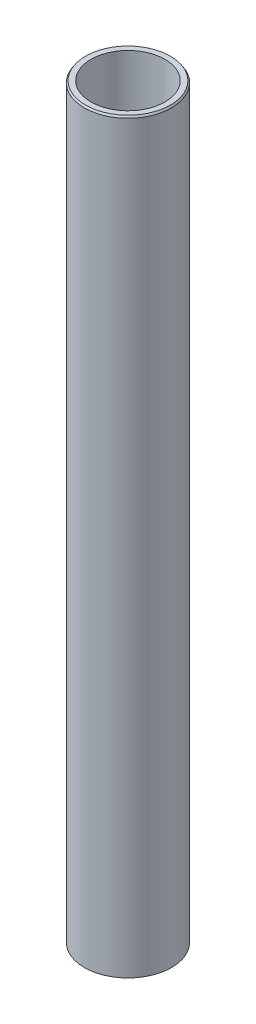
SolidWorks part; units mm, degrees
ref_plane "Front Plane" through (0, 0, 0) normal (0, 0, 1) x (1, 0, 0)
ref_plane "Top Plane" through (0, 0, 0) normal (0, 1, 0) x (1, 0, 0)
ref_plane "Right Plane" through (0, 0, 0) normal (1, 0, 0) x (0, 0, -1)
sketch "Sketch1" plane through (0, 0, 0) normal (0, 1, 0) x (1, 0, 0)
  circle A0 centre (0, 0) radius 35
  dimension "SHAFT_OD" = 70
extrude "Boss-Extrude1" add sketch "Sketch1" along normal blind 600
sketch "Sketch2" plane through (0, 0, 0) normal (0, 1, 0) x (1, 0, 0)
  circle A0 centre (0, 0) radius 29.685
  dimension "BORE_D" = 59.37
extrude "Cut-Extrude1" cut sketch "Sketch2" along normal through all
chamfer "Chamfer1" distance 1.434 angle 34.066 2 edges at (0, 600, 35) (0, 0, 35) first distance on face at (0, 600, 35) first distance on face at (0, 0, 29.685)
